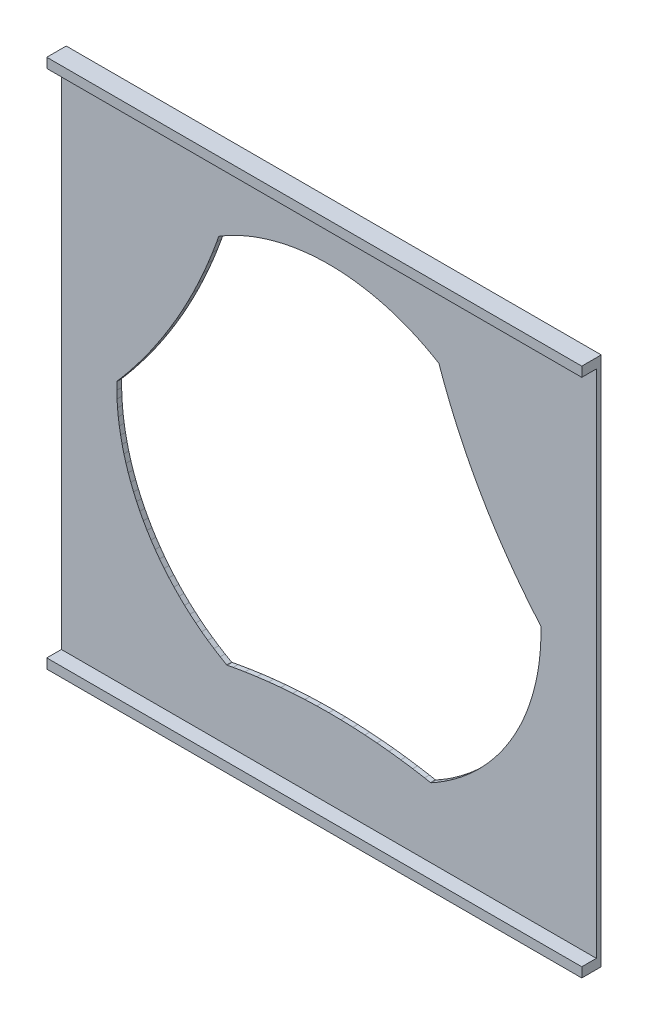
SolidWorks part; units mm, degrees
ref_plane "Front Plane" through (0, 0, 0) normal (0, 0, 1) x (1, 0, 0)
ref_plane "Top Plane" through (0, 0, 0) normal (0, 1, 0) x (1, 0, 0)
ref_plane "Right Plane" through (0, 0, 0) normal (1, 0, 0) x (0, 0, -1)
sketch "Model" plane through (0, 0, 0) normal (0, 0, 1) x (1, 0, 0)
  line L0 (125.677, -154.6098) -> (127.2049, -154.7174)
  line L1 (127.2049, -154.7174) -> (128.7281, -154.8785)
  line L2 (128.7281, -154.8785) -> (130.2447, -155.093)
  line L3 (130.2447, -155.093) -> (131.7528, -155.3606)
  line L4 (131.7528, -155.3606) -> (133.2506, -155.681)
  line L5 (133.2506, -155.681) -> (134.7362, -156.0539)
  line L6 (134.7362, -156.0539) -> (136.2078, -156.4787)
  line L7 (136.2078, -156.4787) -> (137.6636, -156.9549)
  line L8 (137.6636, -156.9549) -> (139.1018, -157.4819)
  line L9 (139.1018, -157.4819) -> (140.5205, -158.0591)
  line L10 (140.5205, -158.0591) -> (141.9181, -158.6858)
  line L11 (141.9181, -158.6858) -> (143.2929, -159.3612)
  line L12 (143.2929, -159.3612) -> (144.6431, -160.0844)
  line L13 (144.6431, -160.0844) -> (145.967, -160.8546)
  line L14 (145.967, -160.8546) -> (145.9831, -160.8702)
  line L15 (145.9831, -160.8702) -> (146.0021, -160.8822)
  line L16 (146.0021, -160.8822) -> (146.0122, -160.8983)
  line L17 (146.0122, -160.8983) -> (146.0259, -160.9116)
  line L18 (146.0259, -160.9116) -> (146.0336, -160.9326)
  line L19 (146.0336, -160.9326) -> (146.0455, -160.9517)
  line L20 (146.0455, -160.9517) -> (146.451, -162.1194)
  line L21 (146.451, -162.1194) -> (147.3137, -164.4362)
  line L22 (147.3137, -164.4362) -> (148.2279, -166.7332)
  line L23 (148.2279, -166.7332) -> (149.193, -169.0092)
  line L24 (149.193, -169.0092) -> (150.2086, -171.2632)
  line L25 (150.2086, -171.2632) -> (151.2742, -173.494)
  line L26 (151.2742, -173.494) -> (152.3892, -175.7006)
  line L27 (152.3892, -175.7006) -> (153.5531, -177.8817)
  line L28 (153.5531, -177.8817) -> (154.7653, -180.0363)
  line L29 (154.7653, -180.0363) -> (156.0251, -182.1634)
  line L30 (156.0251, -182.1634) -> (157.3321, -184.2619)
  line L31 (157.3321, -184.2619) -> (158.6855, -186.3308)
  line L32 (158.6855, -186.3308) -> (160.0847, -188.369)
  line L33 (160.0847, -188.369) -> (161.5289, -190.3755)
  line L34 (161.5289, -190.3755) -> (163.0174, -192.3494)
  line L35 (163.0174, -192.3494) -> (164.5496, -194.2896)
  line L36 (164.5496, -194.2896) -> (166.1246, -196.1952)
  line L37 (166.1246, -196.1952) -> (166.9332, -197.1302)
  line L38 (166.9332, -197.1302) -> (166.9437, -197.15)
  line L39 (166.9437, -197.15) -> (166.9581, -197.1673)
  line L40 (166.9581, -197.1673) -> (166.9627, -197.1857)
  line L41 (166.9627, -197.1857) -> (166.9716, -197.2025)
  line L42 (166.9716, -197.2025) -> (166.9725, -197.2249)
  line L43 (166.9725, -197.2249) -> (166.9779, -197.2467)
  line L44 (166.9779, -197.2467) -> (166.983, -198.7784)
  line L45 (166.983, -198.7784) -> (166.9343, -200.3093)
  line L46 (166.9343, -200.3093) -> (166.8318, -201.8375)
  line L47 (166.8318, -201.8375) -> (166.6757, -203.3612)
  line L48 (166.6757, -203.3612) -> (166.4662, -204.8785)
  line L49 (166.4662, -204.8785) -> (166.2036, -206.3875)
  line L50 (166.2036, -206.3875) -> (165.8881, -207.8864)
  line L51 (165.8881, -207.8864) -> (165.5201, -209.3732)
  line L52 (165.5201, -209.3732) -> (165.1002, -210.8462)
  line L53 (165.1002, -210.8462) -> (164.6288, -212.3036)
  line L54 (164.6288, -212.3036) -> (164.1065, -213.7435)
  line L55 (164.1065, -213.7435) -> (163.534, -215.1641)
  line L56 (163.534, -215.1641) -> (162.9119, -216.5638)
  line L57 (162.9119, -216.5638) -> (162.2411, -217.9408)
  line L58 (162.2411, -217.9408) -> (161.5223, -219.2933)
  line L59 (161.5223, -219.2933) -> (160.7565, -220.6198)
  line L60 (160.7565, -220.6198) -> (159.9445, -221.9186)
  line L61 (159.9445, -221.9186) -> (159.0874, -223.188)
  line L62 (159.0874, -223.188) -> (158.1863, -224.4266)
  line L63 (158.1863, -224.4266) -> (157.2423, -225.6327)
  line L64 (157.2423, -225.6327) -> (156.2564, -226.805)
  line L65 (156.2564, -226.805) -> (155.23, -227.9419)
  line L66 (155.23, -227.9419) -> (154.1643, -229.0421)
  line L67 (154.1643, -229.0421) -> (153.0607, -230.1041)
  line L68 (153.0607, -230.1041) -> (151.9204, -231.1268)
  line L69 (151.9204, -231.1268) -> (150.7449, -232.1087)
  line L70 (150.7449, -232.1087) -> (149.5356, -233.0488)
  line L71 (149.5356, -233.0488) -> (148.2941, -233.9458)
  line L72 (148.2941, -233.9458) -> (147.0218, -234.7987)
  line L73 (147.0218, -234.7987) -> (145.7204, -235.6064)
  line L74 (145.7204, -235.6064) -> (144.3914, -236.3678)
  line L75 (144.3914, -236.3678) -> (144.3698, -236.374)
  line L76 (144.3698, -236.374) -> (144.3499, -236.3845)
  line L77 (144.3499, -236.3845) -> (144.3309, -236.3851)
  line L78 (144.3309, -236.3851) -> (144.3126, -236.3903)
  line L79 (144.3126, -236.3903) -> (144.2905, -236.3865)
  line L80 (144.2905, -236.3865) -> (144.2681, -236.3873)
  line L81 (144.2681, -236.3873) -> (143.054, -236.1546)
  line L82 (143.054, -236.1546) -> (140.6163, -235.7434)
  line L83 (140.6163, -235.7434) -> (138.1699, -235.3866)
  line L84 (138.1699, -235.3866) -> (135.7162, -235.0844)
  line L85 (135.7162, -235.0844) -> (133.2564, -234.8369)
  line L86 (133.2564, -234.8369) -> (130.7917, -234.6443)
  line L87 (130.7917, -234.6443) -> (128.3233, -234.5067)
  line L88 (128.3233, -234.5067) -> (125.8525, -234.4241)
  line L89 (125.8525, -234.4241) -> (123.3804, -234.3965)
  line L90 (123.3804, -234.3965) -> (120.9083, -234.4241)
  line L91 (120.9083, -234.4241) -> (118.4375, -234.5067)
  line L92 (118.4375, -234.5067) -> (115.9691, -234.6443)
  line L93 (115.9691, -234.6443) -> (113.5044, -234.8369)
  line L94 (113.5044, -234.8369) -> (111.0446, -235.0844)
  line L95 (111.0446, -235.0844) -> (108.5909, -235.3866)
  line L96 (108.5909, -235.3866) -> (106.1445, -235.7434)
  line L97 (106.1445, -235.7434) -> (103.7067, -236.1546)
  line L98 (103.7067, -236.1546) -> (102.4927, -236.3873)
  line L99 (102.4927, -236.3873) -> (102.4703, -236.3865)
  line L100 (102.4703, -236.3865) -> (102.4482, -236.3903)
  line L101 (102.4482, -236.3903) -> (102.4299, -236.3851)
  line L102 (102.4299, -236.3851) -> (102.4109, -236.3845)
  line L103 (102.4109, -236.3845) -> (102.391, -236.374)
  line L104 (102.391, -236.374) -> (102.3694, -236.3678)
  line L105 (102.3694, -236.3678) -> (101.0404, -235.6064)
  line L106 (101.0404, -235.6064) -> (99.739, -234.7987)
  line L107 (99.739, -234.7987) -> (98.4667, -233.9458)
  line L108 (98.4667, -233.9458) -> (97.2252, -233.0488)
  line L109 (97.2252, -233.0488) -> (96.0159, -232.1087)
  line L110 (96.0159, -232.1087) -> (94.8404, -231.1268)
  line L111 (94.8404, -231.1268) -> (93.7001, -230.1041)
  line L112 (93.7001, -230.1041) -> (92.5965, -229.0421)
  line L113 (92.5965, -229.0421) -> (91.5308, -227.9419)
  line L114 (91.5308, -227.9419) -> (90.5044, -226.805)
  line L115 (90.5044, -226.805) -> (89.5185, -225.6327)
  line L116 (89.5185, -225.6327) -> (88.5745, -224.4266)
  line L117 (88.5745, -224.4266) -> (87.6733, -223.188)
  line L118 (87.6733, -223.188) -> (86.8163, -221.9186)
  line L119 (86.8163, -221.9186) -> (86.0043, -220.6198)
  line L120 (86.0043, -220.6198) -> (85.2385, -219.2933)
  line L121 (85.2385, -219.2933) -> (84.5197, -217.9408)
  line L122 (84.5197, -217.9408) -> (83.8488, -216.5638)
  line L123 (83.8488, -216.5638) -> (83.2268, -215.1641)
  line L124 (83.2268, -215.1641) -> (82.6542, -213.7435)
  line L125 (82.6542, -213.7435) -> (82.132, -212.3036)
  line L126 (82.132, -212.3036) -> (81.6606, -210.8462)
  line L127 (81.6606, -210.8462) -> (81.2406, -209.3732)
  line L128 (81.2406, -209.3732) -> (80.8727, -207.8864)
  line L129 (80.8727, -207.8864) -> (80.5572, -206.3875)
  line L130 (80.5572, -206.3875) -> (80.2946, -204.8785)
  line L131 (80.2946, -204.8785) -> (80.0851, -203.3612)
  line L132 (80.0851, -203.3612) -> (79.929, -201.8375)
  line L133 (79.929, -201.8375) -> (79.8265, -200.3093)
  line L134 (79.8265, -200.3093) -> (79.7778, -198.7784)
  line L135 (79.7778, -198.7784) -> (79.7828, -197.2467)
  line L136 (79.7828, -197.2467) -> (79.7883, -197.2249)
  line L137 (79.7883, -197.2249) -> (79.7892, -197.2025)
  line L138 (79.7892, -197.2025) -> (79.7981, -197.1857)
  line L139 (79.7981, -197.1857) -> (79.8027, -197.1672)
  line L140 (79.8027, -197.1672) -> (79.8171, -197.15)
  line L141 (79.8171, -197.15) -> (79.8276, -197.1302)
  line L142 (79.8276, -197.1302) -> (80.6361, -196.1952)
  line L143 (80.6361, -196.1952) -> (82.2112, -194.2896)
  line L144 (82.2112, -194.2896) -> (83.7433, -192.3494)
  line L145 (83.7433, -192.3494) -> (85.2319, -190.3755)
  line L146 (85.2319, -190.3755) -> (86.6761, -188.369)
  line L147 (86.6761, -188.369) -> (88.0753, -186.3308)
  line L148 (88.0753, -186.3308) -> (89.4287, -184.2619)
  line L149 (89.4287, -184.2619) -> (90.7356, -182.1634)
  line L150 (90.7356, -182.1634) -> (91.9955, -180.0363)
  line L151 (91.9955, -180.0363) -> (93.2077, -177.8817)
  line L152 (93.2077, -177.8817) -> (94.3716, -175.7005)
  line L153 (94.3716, -175.7005) -> (95.4866, -173.494)
  line L154 (95.4866, -173.494) -> (96.5521, -171.2632)
  line L155 (96.5521, -171.2632) -> (97.5677, -169.0092)
  line L156 (97.5677, -169.0092) -> (98.5329, -166.7332)
  line L157 (98.5329, -166.7332) -> (99.447, -164.4362)
  line L158 (99.447, -164.4362) -> (100.3098, -162.1194)
  line L159 (100.3098, -162.1194) -> (100.7153, -160.9517)
  line L160 (100.7153, -160.9517) -> (100.7272, -160.9326)
  line L161 (100.7272, -160.9326) -> (100.7349, -160.9116)
  line L162 (100.7349, -160.9116) -> (100.7486, -160.8983)
  line L163 (100.7486, -160.8983) -> (100.7587, -160.8822)
  line L164 (100.7587, -160.8822) -> (100.7776, -160.8702)
  line L165 (100.7776, -160.8702) -> (100.7938, -160.8546)
  line L166 (100.7938, -160.8546) -> (102.1177, -160.0844)
  line L167 (102.1177, -160.0844) -> (103.4679, -159.3612)
  line L168 (103.4679, -159.3612) -> (104.8426, -158.6858)
  line L169 (104.8426, -158.6858) -> (106.2403, -158.0591)
  line L170 (106.2403, -158.0591) -> (107.659, -157.4819)
  line L171 (107.659, -157.4819) -> (109.0972, -156.9549)
  line L172 (109.0972, -156.9549) -> (110.553, -156.4787)
  line L173 (110.553, -156.4787) -> (112.0246, -156.0539)
  line L174 (112.0246, -156.0539) -> (113.5102, -155.681)
  line L175 (113.5102, -155.681) -> (115.008, -155.3606)
  line L176 (115.008, -155.3606) -> (116.5161, -155.093)
  line L177 (116.5161, -155.093) -> (118.0327, -154.8785)
  line L178 (118.0327, -154.8785) -> (119.5559, -154.7174)
  line L179 (119.5559, -154.7174) -> (121.0838, -154.6098)
  line L180 (121.0838, -154.6098) -> (122.6145, -154.556)
  line L181 (122.6145, -154.556) -> (124.1462, -154.556)
  line L182 (124.1462, -154.556) -> (125.677, -154.6098)
  line L183 (79.7981, -197.1857) -> (166.9627, -197.1857) construction
  line L184 (144.3309, -236.3851) -> (100.7486, -160.8983) construction
  line L185 (146.0122, -160.8983) -> (102.4299, -236.3851) construction
  line L186 (123.3804, -197.1857) -> (123.3804, -200.0978) construction
  line L187 (122.5397, -198.6417) -> (125.0617, -197.1857) construction
  line L188 (124.221, -198.6417) -> (121.6991, -197.1857) construction
  point P190 (123.3804, -198.1564)
sketch "Sketch2" plane through (0, 0, 0) normal (0, 0, 1) x (1, 0, 0)
  line L1 (65.4557, -250.6328) -> (181.3051, -250.6328)
  line L2 (65.4557, -250.6328) -> (65.4557, -145.68)
  line L3 (65.4557, -145.68) -> (181.3051, -145.68)
  line L4 (181.3051, -250.6328) -> (181.3051, -145.68)
  line L5 (65.4557, -250.6328) -> (181.3051, -145.68) construction
  line L6 (65.4557, -145.68) -> (181.3051, -250.6328) construction
  point P0 (123.3804, -198.1564)
  dimension "D1" = 104.9528
  dimension "D2" = 115.8494
sketch "Sketch3" plane through (0, 0, 0) normal (0, 0, 1) x (1, 0, 0)
  line L0 (80.6361, -196.1952) -> (82.2112, -194.2896) construction
  line L1 (79.8276, -197.1302) -> (80.6361, -196.1952) construction
  line L2 (79.8171, -197.15) -> (79.8276, -197.1302) construction
  line L3 (79.8027, -197.1672) -> (79.8171, -197.15) construction
  line L4 (79.7981, -197.1857) -> (79.8027, -197.1672) construction
  line L5 (79.7892, -197.2025) -> (79.7981, -197.1857) construction
  line L6 (79.7883, -197.2249) -> (79.7892, -197.2025) construction
  line L7 (79.7828, -197.2467) -> (79.7883, -197.2249) construction
  line L8 (79.7778, -198.7784) -> (79.7828, -197.2467) construction
  line L9 (79.8265, -200.3093) -> (79.7778, -198.7784) construction
  line L10 (79.929, -201.8375) -> (79.8265, -200.3093) construction
  line L11 (80.0851, -203.3612) -> (79.929, -201.8375) construction
  line L12 (80.2946, -204.8785) -> (80.0851, -203.3612) construction
  line L13 (80.5572, -206.3875) -> (80.2946, -204.8785) construction
  line L14 (80.8727, -207.8864) -> (80.5572, -206.3875) construction
  line L15 (81.2406, -209.3732) -> (80.8727, -207.8864) construction
  line L16 (81.6606, -210.8462) -> (81.2406, -209.3732) construction
  line L17 (82.132, -212.3036) -> (81.6606, -210.8462) construction
  line L18 (82.6542, -213.7435) -> (82.132, -212.3036) construction
  line L19 (83.2268, -215.1641) -> (82.6542, -213.7435) construction
  line L20 (83.8488, -216.5638) -> (83.2268, -215.1641) construction
  line L21 (84.5197, -217.9408) -> (83.8488, -216.5638) construction
  line L22 (85.2385, -219.2933) -> (84.5197, -217.9408) construction
  line L23 (86.0043, -220.6198) -> (85.2385, -219.2933) construction
  line L24 (86.8163, -221.9186) -> (86.0043, -220.6198) construction
  line L25 (87.6733, -223.188) -> (86.8163, -221.9186) construction
  line L26 (88.5745, -224.4266) -> (87.6733, -223.188) construction
  line L27 (89.5185, -225.6327) -> (88.5745, -224.4266) construction
  line L28 (90.5044, -226.805) -> (89.5185, -225.6327) construction
  line L29 (91.5308, -227.9419) -> (90.5044, -226.805) construction
  line L30 (92.5965, -229.0421) -> (91.5308, -227.9419) construction
  line L31 (93.7001, -230.1041) -> (92.5965, -229.0421) construction
  line L32 (94.8404, -231.1268) -> (93.7001, -230.1041) construction
  line L33 (96.0159, -232.1087) -> (94.8404, -231.1268) construction
  line L34 (97.2252, -233.0488) -> (96.0159, -232.1087) construction
  line L35 (98.4667, -233.9458) -> (97.2252, -233.0488) construction
  line L36 (99.739, -234.7987) -> (98.4667, -233.9458) construction
  line L37 (101.0404, -235.6064) -> (99.739, -234.7987) construction
  line L38 (102.3694, -236.3678) -> (101.0404, -235.6064) construction
  line L39 (102.391, -236.374) -> (102.3694, -236.3678) construction
  line L40 (102.4109, -236.3845) -> (102.391, -236.374) construction
  line L41 (102.4299, -236.3851) -> (102.4109, -236.3845) construction
  line L42 (102.4482, -236.3903) -> (102.4299, -236.3851) construction
  line L43 (102.4703, -236.3865) -> (102.4482, -236.3903) construction
  line L44 (102.4927, -236.3873) -> (102.4703, -236.3865) construction
  line L45 (103.7067, -236.1546) -> (102.4927, -236.3873) construction
  line L46 (106.1445, -235.7434) -> (103.7067, -236.1546) construction
  line L47 (108.5909, -235.3866) -> (106.1445, -235.7434) construction
  line L48 (111.0446, -235.0844) -> (108.5909, -235.3866) construction
  line L49 (113.5044, -234.8369) -> (111.0446, -235.0844) construction
  line L50 (115.9691, -234.6443) -> (113.5044, -234.8369) construction
  line L51 (118.4375, -234.5067) -> (115.9691, -234.6443) construction
  line L52 (120.9083, -234.4241) -> (118.4375, -234.5067) construction
  line L53 (123.3804, -234.3965) -> (120.9083, -234.4241) construction
  line L54 (125.8525, -234.4241) -> (123.3804, -234.3965) construction
  line L55 (128.3233, -234.5067) -> (125.8525, -234.4241) construction
  line L56 (130.7917, -234.6443) -> (128.3233, -234.5067) construction
  line L57 (133.2564, -234.8369) -> (130.7917, -234.6443) construction
  line L58 (135.7162, -235.0844) -> (133.2564, -234.8369) construction
  line L59 (138.1699, -235.3866) -> (135.7162, -235.0844) construction
  line L60 (140.6163, -235.7434) -> (138.1699, -235.3866) construction
  line L61 (143.054, -236.1546) -> (140.6163, -235.7434) construction
  line L62 (144.2681, -236.3873) -> (143.054, -236.1546) construction
  line L63 (144.2905, -236.3865) -> (144.2681, -236.3873) construction
  line L64 (144.3126, -236.3903) -> (144.2905, -236.3865) construction
  line L65 (144.3309, -236.3851) -> (144.3126, -236.3903) construction
  line L66 (144.3499, -236.3845) -> (144.3309, -236.3851) construction
  line L67 (144.3698, -236.374) -> (144.3499, -236.3845) construction
  line L68 (144.3914, -236.3678) -> (144.3698, -236.374) construction
  line L69 (145.7204, -235.6064) -> (144.3914, -236.3678) construction
  line L70 (147.0218, -234.7987) -> (145.7204, -235.6064) construction
  line L71 (148.2941, -233.9458) -> (147.0218, -234.7987) construction
  line L72 (149.5356, -233.0488) -> (148.2941, -233.9458) construction
  line L73 (150.7449, -232.1087) -> (149.5356, -233.0488) construction
  line L74 (151.9204, -231.1268) -> (150.7449, -232.1087) construction
  line L75 (153.0607, -230.1041) -> (151.9204, -231.1268) construction
  line L76 (154.1643, -229.0421) -> (153.0607, -230.1041) construction
  line L77 (155.23, -227.9419) -> (154.1643, -229.0421) construction
  line L78 (156.2564, -226.805) -> (155.23, -227.9419) construction
  line L79 (157.2423, -225.6327) -> (156.2564, -226.805) construction
  line L80 (158.1863, -224.4266) -> (157.2423, -225.6327) construction
  line L81 (159.0874, -223.188) -> (158.1863, -224.4266) construction
  line L82 (159.9445, -221.9186) -> (159.0874, -223.188) construction
  line L83 (160.7565, -220.6198) -> (159.9445, -221.9186) construction
  line L84 (161.5223, -219.2933) -> (160.7565, -220.6198) construction
  line L85 (162.2411, -217.9408) -> (161.5223, -219.2933) construction
  line L86 (162.9119, -216.5638) -> (162.2411, -217.9408) construction
  line L87 (163.534, -215.1641) -> (162.9119, -216.5638) construction
  line L88 (164.1065, -213.7435) -> (163.534, -215.1641) construction
  line L89 (164.6288, -212.3036) -> (164.1065, -213.7435) construction
  line L90 (165.1002, -210.8462) -> (164.6288, -212.3036) construction
  line L91 (165.5201, -209.3732) -> (165.1002, -210.8462) construction
  line L92 (165.8881, -207.8864) -> (165.5201, -209.3732) construction
  line L93 (166.2036, -206.3875) -> (165.8881, -207.8864) construction
  line L94 (166.4662, -204.8785) -> (166.2036, -206.3875) construction
  line L95 (166.6757, -203.3612) -> (166.4662, -204.8785) construction
  line L96 (166.8318, -201.8375) -> (166.6757, -203.3612) construction
  line L97 (166.9343, -200.3093) -> (166.8318, -201.8375) construction
  line L98 (166.983, -198.7784) -> (166.9343, -200.3093) construction
  line L99 (166.9779, -197.2467) -> (166.983, -198.7784) construction
  line L100 (166.9725, -197.2249) -> (166.9779, -197.2467) construction
  line L101 (166.9716, -197.2025) -> (166.9725, -197.2249) construction
  line L102 (166.9627, -197.1857) -> (166.9716, -197.2025) construction
  line L103 (166.9581, -197.1673) -> (166.9627, -197.1857) construction
  line L104 (166.9437, -197.15) -> (166.9581, -197.1673) construction
  line L105 (166.9332, -197.1302) -> (166.9437, -197.15) construction
  line L106 (166.1246, -196.1952) -> (166.9332, -197.1302) construction
  line L107 (164.5496, -194.2896) -> (166.1246, -196.1952) construction
  line L108 (163.0174, -192.3494) -> (164.5496, -194.2896) construction
  line L109 (161.5289, -190.3755) -> (163.0174, -192.3494) construction
  line L110 (160.0847, -188.369) -> (161.5289, -190.3755) construction
  line L111 (158.6855, -186.3308) -> (160.0847, -188.369) construction
  line L112 (157.3321, -184.2619) -> (158.6855, -186.3308) construction
  line L113 (156.0251, -182.1634) -> (157.3321, -184.2619) construction
  line L114 (154.7653, -180.0363) -> (156.0251, -182.1634) construction
  line L115 (153.5531, -177.8817) -> (154.7653, -180.0363) construction
  line L116 (152.3892, -175.7006) -> (153.5531, -177.8817) construction
  line L117 (151.2742, -173.494) -> (152.3892, -175.7006) construction
  line L118 (150.2086, -171.2632) -> (151.2742, -173.494) construction
  line L119 (149.193, -169.0092) -> (150.2086, -171.2632) construction
  line L120 (148.2279, -166.7332) -> (149.193, -169.0092) construction
  line L121 (147.3137, -164.4362) -> (148.2279, -166.7332) construction
  line L122 (146.451, -162.1194) -> (147.3137, -164.4362) construction
  line L123 (146.0455, -160.9517) -> (146.451, -162.1194) construction
  line L124 (146.0336, -160.9326) -> (146.0455, -160.9517) construction
  line L125 (146.0259, -160.9116) -> (146.0336, -160.9326) construction
  line L126 (146.0122, -160.8983) -> (146.0259, -160.9116) construction
  line L127 (146.0021, -160.8822) -> (146.0122, -160.8983) construction
  line L128 (145.9831, -160.8702) -> (146.0021, -160.8822) construction
  line L129 (145.967, -160.8546) -> (145.9831, -160.8702) construction
  line L130 (144.6431, -160.0844) -> (145.967, -160.8546) construction
  line L131 (143.2929, -159.3612) -> (144.6431, -160.0844) construction
  line L132 (141.9181, -158.6858) -> (143.2929, -159.3612) construction
  line L133 (140.5205, -158.0591) -> (141.9181, -158.6858) construction
  line L134 (139.1018, -157.4819) -> (140.5205, -158.0591) construction
  line L135 (137.6636, -156.9549) -> (139.1018, -157.4819) construction
  line L136 (136.2078, -156.4787) -> (137.6636, -156.9549) construction
  line L137 (134.7362, -156.0539) -> (136.2078, -156.4787) construction
  line L138 (133.2506, -155.681) -> (134.7362, -156.0539) construction
  line L139 (131.7528, -155.3606) -> (133.2506, -155.681) construction
  line L140 (130.2447, -155.093) -> (131.7528, -155.3606) construction
  line L141 (128.7281, -154.8785) -> (130.2447, -155.093) construction
  line L142 (127.2049, -154.7174) -> (128.7281, -154.8785) construction
  line L143 (125.677, -154.6098) -> (127.2049, -154.7174) construction
  line L144 (124.1462, -154.556) -> (125.677, -154.6098) construction
  line L145 (122.6145, -154.556) -> (124.1462, -154.556) construction
  line L146 (121.0838, -154.6098) -> (122.6145, -154.556) construction
  line L147 (119.5559, -154.7174) -> (121.0838, -154.6098) construction
  line L148 (118.0327, -154.8785) -> (119.5559, -154.7174) construction
  line L149 (116.5161, -155.093) -> (118.0327, -154.8785) construction
  line L150 (115.008, -155.3606) -> (116.5161, -155.093) construction
  line L151 (113.5102, -155.681) -> (115.008, -155.3606) construction
  line L152 (112.0246, -156.0539) -> (113.5102, -155.681) construction
  line L153 (110.553, -156.4787) -> (112.0246, -156.0539) construction
  line L154 (109.0972, -156.9549) -> (110.553, -156.4787) construction
  line L155 (107.659, -157.4819) -> (109.0972, -156.9549) construction
  line L156 (106.2403, -158.0591) -> (107.659, -157.4819) construction
  line L157 (104.8426, -158.6858) -> (106.2403, -158.0591) construction
  line L158 (103.4679, -159.3612) -> (104.8426, -158.6858) construction
  line L159 (102.1177, -160.0844) -> (103.4679, -159.3612) construction
  line L160 (100.7938, -160.8546) -> (102.1177, -160.0844) construction
  line L161 (100.7776, -160.8702) -> (100.7938, -160.8546) construction
  line L162 (100.7587, -160.8822) -> (100.7776, -160.8702) construction
  line L163 (100.7486, -160.8983) -> (100.7587, -160.8822) construction
  line L164 (100.7349, -160.9116) -> (100.7486, -160.8983) construction
  line L165 (100.7272, -160.9326) -> (100.7349, -160.9116) construction
  line L166 (100.7153, -160.9517) -> (100.7272, -160.9326) construction
  line L167 (100.3098, -162.1194) -> (100.7153, -160.9517) construction
  line L168 (99.447, -164.4362) -> (100.3098, -162.1194) construction
  line L169 (98.5329, -166.7332) -> (99.447, -164.4362) construction
  line L170 (97.5677, -169.0092) -> (98.5329, -166.7332) construction
  line L171 (96.5521, -171.2632) -> (97.5677, -169.0092) construction
  line L172 (95.4866, -173.494) -> (96.5521, -171.2632) construction
  line L173 (94.3716, -175.7005) -> (95.4866, -173.494) construction
  line L174 (93.2077, -177.8817) -> (94.3716, -175.7005) construction
  line L175 (91.9955, -180.0363) -> (93.2077, -177.8817) construction
  line L176 (90.7356, -182.1634) -> (91.9955, -180.0363) construction
  line L177 (89.4287, -184.2619) -> (90.7356, -182.1634) construction
  line L178 (88.0753, -186.3308) -> (89.4287, -184.2619) construction
  line L179 (86.6761, -188.369) -> (88.0753, -186.3308) construction
  line L180 (85.2319, -190.3755) -> (86.6761, -188.369) construction
  line L181 (83.7433, -192.3494) -> (85.2319, -190.3755) construction
  line L182 (82.2112, -194.2896) -> (83.7433, -192.3494) construction
  line L183 (80.6361, -196.1952) -> (82.2112, -194.2896)
  line L184 (79.8276, -197.1302) -> (80.6361, -196.1952)
  line L185 (79.8171, -197.15) -> (79.8276, -197.1302)
  line L186 (79.8027, -197.1672) -> (79.8171, -197.15)
  line L187 (79.7981, -197.1857) -> (79.8027, -197.1672)
  line L188 (79.7892, -197.2025) -> (79.7981, -197.1857)
  line L189 (79.7883, -197.2249) -> (79.7892, -197.2025)
  line L190 (79.7828, -197.2467) -> (79.7883, -197.2249)
  line L191 (79.7778, -198.7784) -> (79.7828, -197.2467)
  line L192 (79.8265, -200.3093) -> (79.7778, -198.7784)
  line L193 (79.929, -201.8375) -> (79.8265, -200.3093)
  line L194 (80.0851, -203.3612) -> (79.929, -201.8375)
  line L195 (80.2946, -204.8785) -> (80.0851, -203.3612)
  line L196 (80.5572, -206.3875) -> (80.2946, -204.8785)
  line L197 (80.8727, -207.8864) -> (80.5572, -206.3875)
  line L198 (81.2406, -209.3732) -> (80.8727, -207.8864)
  line L199 (81.6606, -210.8462) -> (81.2406, -209.3732)
  line L200 (82.132, -212.3036) -> (81.6606, -210.8462)
  line L201 (82.6542, -213.7435) -> (82.132, -212.3036)
  line L202 (83.2268, -215.1641) -> (82.6542, -213.7435)
  line L203 (83.8488, -216.5638) -> (83.2268, -215.1641)
  line L204 (84.5197, -217.9408) -> (83.8488, -216.5638)
  line L205 (85.2385, -219.2933) -> (84.5197, -217.9408)
  line L206 (86.0043, -220.6198) -> (85.2385, -219.2933)
  line L207 (86.8163, -221.9186) -> (86.0043, -220.6198)
  line L208 (87.6733, -223.188) -> (86.8163, -221.9186)
  line L209 (88.5745, -224.4266) -> (87.6733, -223.188)
  line L210 (89.5185, -225.6327) -> (88.5745, -224.4266)
  line L211 (90.5044, -226.805) -> (89.5185, -225.6327)
  line L212 (91.5308, -227.9419) -> (90.5044, -226.805)
  line L213 (92.5965, -229.0421) -> (91.5308, -227.9419)
  line L214 (93.7001, -230.1041) -> (92.5965, -229.0421)
  line L215 (94.8404, -231.1268) -> (93.7001, -230.1041)
  line L216 (96.0159, -232.1087) -> (94.8404, -231.1268)
  line L217 (97.2252, -233.0488) -> (96.0159, -232.1087)
  line L218 (98.4667, -233.9458) -> (97.2252, -233.0488)
  line L219 (99.739, -234.7987) -> (98.4667, -233.9458)
  line L220 (101.0404, -235.6064) -> (99.739, -234.7987)
  line L221 (102.3694, -236.3678) -> (101.0404, -235.6064)
  line L222 (102.391, -236.374) -> (102.3694, -236.3678)
  line L223 (102.4109, -236.3845) -> (102.391, -236.374)
  line L224 (102.4299, -236.3851) -> (102.4109, -236.3845)
  line L225 (102.4482, -236.3903) -> (102.4299, -236.3851)
  line L226 (102.4703, -236.3865) -> (102.4482, -236.3903)
  line L227 (102.4927, -236.3873) -> (102.4703, -236.3865)
  line L228 (103.7067, -236.1546) -> (102.4927, -236.3873)
  line L229 (106.1445, -235.7434) -> (103.7067, -236.1546)
  line L230 (108.5909, -235.3866) -> (106.1445, -235.7434)
  line L231 (111.0446, -235.0844) -> (108.5909, -235.3866)
  line L232 (113.5044, -234.8369) -> (111.0446, -235.0844)
  line L233 (115.9691, -234.6443) -> (113.5044, -234.8369)
  line L234 (118.4375, -234.5067) -> (115.9691, -234.6443)
  line L235 (120.9083, -234.4241) -> (118.4375, -234.5067)
  line L236 (123.3804, -234.3965) -> (120.9083, -234.4241)
  line L237 (125.8525, -234.4241) -> (123.3804, -234.3965)
  line L238 (128.3233, -234.5067) -> (125.8525, -234.4241)
  line L239 (130.7917, -234.6443) -> (128.3233, -234.5067)
  line L240 (133.2564, -234.8369) -> (130.7917, -234.6443)
  line L241 (135.7162, -235.0844) -> (133.2564, -234.8369)
  line L242 (138.1699, -235.3866) -> (135.7162, -235.0844)
  line L243 (140.6163, -235.7434) -> (138.1699, -235.3866)
  line L244 (143.054, -236.1546) -> (140.6163, -235.7434)
  line L245 (144.2681, -236.3873) -> (143.054, -236.1546)
  line L246 (144.2905, -236.3865) -> (144.2681, -236.3873)
  line L247 (144.3126, -236.3903) -> (144.2905, -236.3865)
  line L248 (144.3309, -236.3851) -> (144.3126, -236.3903)
  line L249 (144.3499, -236.3845) -> (144.3309, -236.3851)
  line L250 (144.3698, -236.374) -> (144.3499, -236.3845)
  line L251 (144.3914, -236.3678) -> (144.3698, -236.374)
  line L252 (145.7204, -235.6064) -> (144.3914, -236.3678)
  line L253 (147.0218, -234.7987) -> (145.7204, -235.6064)
  line L254 (148.2941, -233.9458) -> (147.0218, -234.7987)
  line L255 (149.5356, -233.0488) -> (148.2941, -233.9458)
  line L256 (150.7449, -232.1087) -> (149.5356, -233.0488)
  line L257 (151.9204, -231.1268) -> (150.7449, -232.1087)
  line L258 (153.0607, -230.1041) -> (151.9204, -231.1268)
  line L259 (154.1643, -229.0421) -> (153.0607, -230.1041)
  line L260 (155.23, -227.9419) -> (154.1643, -229.0421)
  line L261 (156.2564, -226.805) -> (155.23, -227.9419)
  line L262 (157.2423, -225.6327) -> (156.2564, -226.805)
  line L263 (158.1863, -224.4266) -> (157.2423, -225.6327)
  line L264 (159.0874, -223.188) -> (158.1863, -224.4266)
  line L265 (159.9445, -221.9186) -> (159.0874, -223.188)
  line L266 (160.7565, -220.6198) -> (159.9445, -221.9186)
  line L267 (161.5223, -219.2933) -> (160.7565, -220.6198)
  line L268 (162.2411, -217.9408) -> (161.5223, -219.2933)
  line L269 (162.9119, -216.5638) -> (162.2411, -217.9408)
  line L270 (163.534, -215.1641) -> (162.9119, -216.5638)
  line L271 (164.1065, -213.7435) -> (163.534, -215.1641)
  line L272 (164.6288, -212.3036) -> (164.1065, -213.7435)
  line L273 (165.1002, -210.8462) -> (164.6288, -212.3036)
  line L274 (165.5201, -209.3732) -> (165.1002, -210.8462)
  line L275 (165.8881, -207.8864) -> (165.5201, -209.3732)
  line L276 (166.2036, -206.3875) -> (165.8881, -207.8864)
  line L277 (166.4662, -204.8785) -> (166.2036, -206.3875)
  line L278 (166.6757, -203.3612) -> (166.4662, -204.8785)
  line L279 (166.8318, -201.8375) -> (166.6757, -203.3612)
  line L280 (166.9343, -200.3093) -> (166.8318, -201.8375)
  line L281 (166.983, -198.7784) -> (166.9343, -200.3093)
  line L282 (166.9779, -197.2467) -> (166.983, -198.7784)
  line L283 (166.9725, -197.2249) -> (166.9779, -197.2467)
  line L284 (166.9716, -197.2025) -> (166.9725, -197.2249)
  line L285 (166.9627, -197.1857) -> (166.9716, -197.2025)
  line L286 (166.9581, -197.1673) -> (166.9627, -197.1857)
  line L287 (166.9437, -197.15) -> (166.9581, -197.1673)
  line L288 (166.9332, -197.1302) -> (166.9437, -197.15)
  line L289 (166.1246, -196.1952) -> (166.9332, -197.1302)
  line L290 (164.5496, -194.2896) -> (166.1246, -196.1952)
  line L291 (163.0174, -192.3494) -> (164.5496, -194.2896)
  line L292 (161.5289, -190.3755) -> (163.0174, -192.3494)
  line L293 (160.0847, -188.369) -> (161.5289, -190.3755)
  line L294 (158.6855, -186.3308) -> (160.0847, -188.369)
  line L295 (157.3321, -184.2619) -> (158.6855, -186.3308)
  line L296 (156.0251, -182.1634) -> (157.3321, -184.2619)
  line L297 (154.7653, -180.0363) -> (156.0251, -182.1634)
  line L298 (153.5531, -177.8817) -> (154.7653, -180.0363)
  line L299 (152.3892, -175.7006) -> (153.5531, -177.8817)
  line L300 (151.2742, -173.494) -> (152.3892, -175.7006)
  line L301 (150.2086, -171.2632) -> (151.2742, -173.494)
  line L302 (149.193, -169.0092) -> (150.2086, -171.2632)
  line L303 (148.2279, -166.7332) -> (149.193, -169.0092)
  line L304 (147.3137, -164.4362) -> (148.2279, -166.7332)
  line L305 (146.451, -162.1194) -> (147.3137, -164.4362)
  line L306 (146.0455, -160.9517) -> (146.451, -162.1194)
  line L307 (146.0336, -160.9326) -> (146.0455, -160.9517)
  line L308 (146.0259, -160.9116) -> (146.0336, -160.9326)
  line L309 (146.0122, -160.8983) -> (146.0259, -160.9116)
  line L310 (146.0021, -160.8822) -> (146.0122, -160.8983)
  line L311 (145.9831, -160.8702) -> (146.0021, -160.8822)
  line L312 (145.967, -160.8546) -> (145.9831, -160.8702)
  line L313 (144.6431, -160.0844) -> (145.967, -160.8546)
  line L314 (143.2929, -159.3612) -> (144.6431, -160.0844)
  line L315 (141.9181, -158.6858) -> (143.2929, -159.3612)
  line L316 (140.5205, -158.0591) -> (141.9181, -158.6858)
  line L317 (139.1018, -157.4819) -> (140.5205, -158.0591)
  line L318 (137.6636, -156.9549) -> (139.1018, -157.4819)
  line L319 (136.2078, -156.4787) -> (137.6636, -156.9549)
  line L320 (134.7362, -156.0539) -> (136.2078, -156.4787)
  line L321 (133.2506, -155.681) -> (134.7362, -156.0539)
  line L322 (131.7528, -155.3606) -> (133.2506, -155.681)
  line L323 (130.2447, -155.093) -> (131.7528, -155.3606)
  line L324 (128.7281, -154.8785) -> (130.2447, -155.093)
  line L325 (127.2049, -154.7174) -> (128.7281, -154.8785)
  line L326 (125.677, -154.6098) -> (127.2049, -154.7174)
  line L327 (124.1462, -154.556) -> (125.677, -154.6098)
  line L328 (122.6145, -154.556) -> (124.1462, -154.556)
  line L329 (121.0838, -154.6098) -> (122.6145, -154.556)
  line L330 (119.5559, -154.7174) -> (121.0838, -154.6098)
  line L331 (118.0327, -154.8785) -> (119.5559, -154.7174)
  line L332 (116.5161, -155.093) -> (118.0327, -154.8785)
  line L333 (115.008, -155.3606) -> (116.5161, -155.093)
  line L334 (113.5102, -155.681) -> (115.008, -155.3606)
  line L335 (112.0246, -156.0539) -> (113.5102, -155.681)
  line L336 (110.553, -156.4787) -> (112.0246, -156.0539)
  line L337 (109.0972, -156.9549) -> (110.553, -156.4787)
  line L338 (107.659, -157.4819) -> (109.0972, -156.9549)
  line L339 (106.2403, -158.0591) -> (107.659, -157.4819)
  line L340 (104.8426, -158.6858) -> (106.2403, -158.0591)
  line L341 (103.4679, -159.3612) -> (104.8426, -158.6858)
  line L342 (102.1177, -160.0844) -> (103.4679, -159.3612)
  line L343 (100.7938, -160.8546) -> (102.1177, -160.0844)
  line L344 (100.7776, -160.8702) -> (100.7938, -160.8546)
  line L345 (100.7587, -160.8822) -> (100.7776, -160.8702)
  line L346 (100.7486, -160.8983) -> (100.7587, -160.8822)
  line L347 (100.7349, -160.9116) -> (100.7486, -160.8983)
  line L348 (100.7272, -160.9326) -> (100.7349, -160.9116)
  line L349 (100.7153, -160.9517) -> (100.7272, -160.9326)
  line L350 (100.3098, -162.1194) -> (100.7153, -160.9517)
  line L351 (99.447, -164.4362) -> (100.3098, -162.1194)
  line L352 (98.5329, -166.7332) -> (99.447, -164.4362)
  line L353 (97.5677, -169.0092) -> (98.5329, -166.7332)
  line L354 (96.5521, -171.2632) -> (97.5677, -169.0092)
  line L355 (95.4866, -173.494) -> (96.5521, -171.2632)
  line L356 (94.3716, -175.7005) -> (95.4866, -173.494)
  line L357 (93.2077, -177.8817) -> (94.3716, -175.7005)
  line L358 (91.9955, -180.0363) -> (93.2077, -177.8817)
  line L359 (90.7356, -182.1634) -> (91.9955, -180.0363)
  line L360 (89.4287, -184.2619) -> (90.7356, -182.1634)
  line L361 (88.0753, -186.3308) -> (89.4287, -184.2619)
  line L362 (86.6761, -188.369) -> (88.0753, -186.3308)
  line L363 (85.2319, -190.3755) -> (86.6761, -188.369)
  line L364 (83.7433, -192.3494) -> (85.2319, -190.3755)
  line L365 (82.2112, -194.2896) -> (83.7433, -192.3494)
extrude "Boss-Extrude1" add sketch "Sketch2" along normal blind 1
extrude "Cut-Extrude2" cut sketch "Sketch3" along normal through all
sketch "Sketch4" plane through (0, 0, 0) normal (0, 0, 1) x (1, 0, 0)
  line L1 (181.3051, -250.6328) -> (65.4557, -250.6328)
  line L2 (181.3051, -250.6328) -> (181.3051, -145.68)
  line L3 (181.3051, -145.68) -> (65.4557, -145.68)
  line L4 (65.4557, -250.6328) -> (65.4557, -145.68)
  line L5 (181.3051, -250.6328) -> (65.4557, -145.68) construction
  line L6 (181.3051, -145.68) -> (65.4557, -250.6328) construction
  line L7 (183.5127, -252.6328) -> (63.248, -252.6328)
  line L8 (183.5127, -252.6328) -> (183.5127, -143.68)
  line L9 (183.5127, -143.68) -> (63.248, -143.68)
  line L10 (63.248, -252.6328) -> (63.248, -143.68)
  line L11 (183.5127, -252.6328) -> (63.248, -143.68) construction
  line L12 (183.5127, -143.68) -> (63.248, -252.6328) construction
  point P0 (123.3804, -198.1564)
  point P7 (123.3804, -198.1564)
  dimension "D1" = 2
extrude "Boss-Extrude2" add sketch "Sketch4" along normal blind 4
sketch "Sketch5" plane through (0, 0, 0) normal (0, 0, 1) x (1, 0, 0)
  line L0 (183.5127, -143.68) -> (63.248, -143.68) construction
  line L1 (178.3804, -252.6328) -> (68.3804, -252.6328)
  line L2 (178.3804, -252.6328) -> (178.3804, -143.68)
  line L3 (178.3804, -143.68) -> (68.3804, -143.68)
  line L4 (68.3804, -252.6328) -> (68.3804, -143.68)
  line L5 (178.3804, -252.6328) -> (68.3804, -143.68) construction
  line L6 (178.3804, -143.68) -> (68.3804, -252.6328) construction
  point P0 (123.3804, -198.1564)
  dimension "D1" = 110
extrude "Cut-Extrude3" cut sketch "Sketch5" along normal through all flip side to cut
